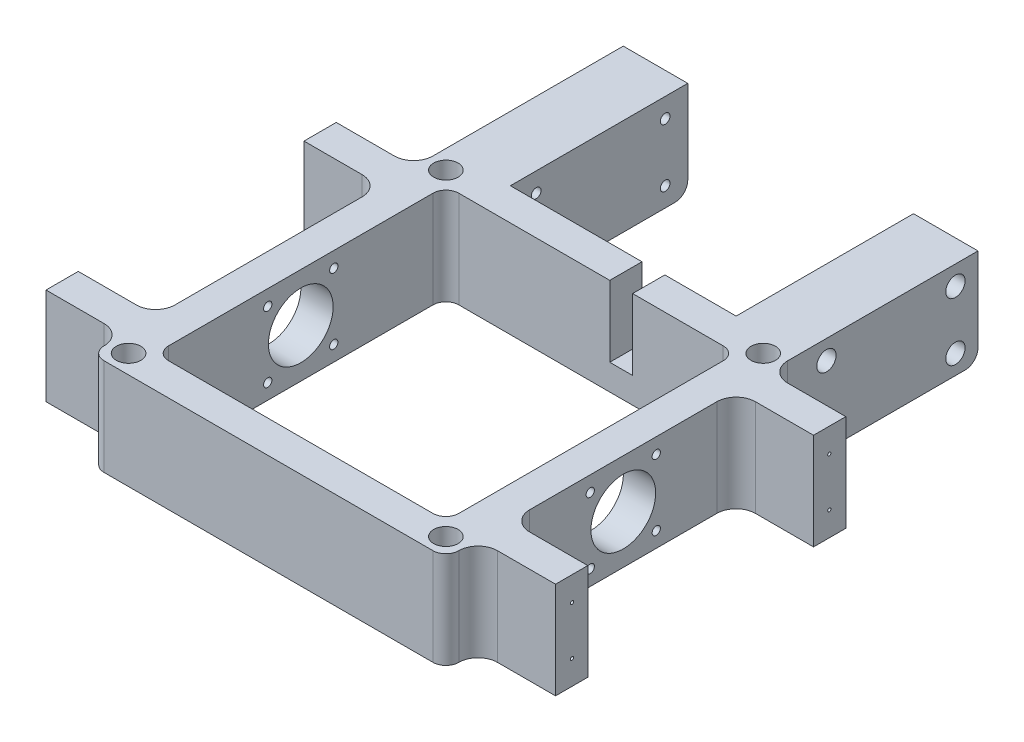
SolidWorks part; units mm, degrees
ref_plane "Front Plane" through (0, 0, 0) normal (0, 0, 1) x (1, 0, 0)
ref_plane "Top Plane" through (0, 0, 0) normal (0, 1, 0) x (1, 0, 0)
ref_plane "Right Plane" through (0, 0, 0) normal (1, 0, 0) x (0, 0, -1)
sketch "Sketch1" plane through (0, 0, 0) normal (0, 1, 0) x (1, 0, 0)
  line L1 (-69.85, 69.85) -> (69.85, 69.85)
  line L2 (-69.85, 69.85) -> (-69.85, -69.85)
  line L3 (-69.85, -69.85) -> (69.85, -69.85)
  line L4 (69.85, 69.85) -> (69.85, -69.85)
  line L5 (-69.85, 69.85) -> (69.85, -69.85) construction
  line L6 (-69.85, -69.85) -> (69.85, 69.85) construction
  line L7 (-69.85, 69.85) -> (-31.75, 69.85)
  line L31 (-69.85, 69.85) -> (-44.45, 69.85)
  line L32 (-69.85, 69.85) -> (-69.85, 139.7)
  line L33 (-69.85, 139.7) -> (-44.45, 139.7)
  line L34 (-44.45, 69.85) -> (-44.45, 139.7)
  line L35 (69.85, 69.85) -> (44.45, 69.85)
  line L36 (69.85, 69.85) -> (69.85, 139.7)
  line L37 (69.85, 139.7) -> (44.45, 139.7)
  line L38 (44.45, 69.85) -> (44.45, 139.7)
  line L39 (-57.15, 57.15) -> (57.15, 57.15)
  line L40 (-57.15, 57.15) -> (-57.15, -57.15)
  line L41 (-57.15, -57.15) -> (57.15, -57.15)
  line L42 (57.15, 57.15) -> (57.15, -57.15)
  line L43 (-57.15, 57.15) -> (57.15, -57.15) construction
  line L44 (-57.15, -57.15) -> (57.15, 57.15) construction
  circle A0 centre (-62.484, -62.484) radius 7.366 construction
  circle A1 centre (-62.484, -62.484) radius 4.826
  circle A2 centre (62.484, -62.484) radius 4.826
  circle A3 centre (62.484, -62.484) radius 7.366 construction
  circle A4 centre (-62.484, 62.484) radius 4.826
  circle A5 centre (-62.484, 62.484) radius 7.366 construction
  circle A6 centre (62.484, 62.484) radius 7.366 construction
  circle A7 centre (62.484, 62.484) radius 4.826
  point P0 (0, 0)
  point P23 (0, 0)
  dimension "D7" = 9.652
  dimension "D8" = 14.732
  dimension "D9" = 9.652
  dimension "D10" = 14.732
  dimension "D11" = 9.652
  dimension "D12" = 14.732
  dimension "D13" = 9.652
  dimension "D15" = 114.3
  dimension "D16" = 114.3
  dimension "D6" = 14.732
  dimension "D1" = 139.7
  dimension "D2" = 139.7
  dimension "D3" = 69.85
  dimension "D4" = 69.85
  dimension "D5" = 88.9
extrude "Boss-Extrude2" add sketch "Sketch1" along normal blind 38.1 contours L1 L34 L33 L32 | L4 L1 L7 L2 L3 A7 A4 A2 A1 L39 L42 L41 L40 | L1 | L35 L38 L37 L36 region at (-57.15, 0, -104.775) region at (-57.15, 0, -67.8743) region at (57.15, 0, -104.775)
sketch "Sketch5" plane through (69.85, 0, 0) normal (1, 0, 0) x (0, 0, -1)
  line L2 (139.7, 38.1) -> (-69.85, 38.1) construction
  line L3 (-13, 6.05) -> (13, 6.05) construction
  line L4 (-13, 6.05) -> (-13, 32.05) construction
  line L5 (-13, 32.05) -> (13, 32.05) construction
  line L6 (13, 6.05) -> (13, 32.05) construction
  line L7 (-13, 6.05) -> (13, 32.05) construction
  line L8 (-13, 32.05) -> (13, 6.05) construction
  circle A0 centre (0, 19.05) radius 12.75
  circle A1 centre (-13, 32.05) radius 1.6319
  circle A2 centre (13, 32.05) radius 1.6319
  circle A3 centre (13, 6.05) radius 1.632
  circle A4 centre (-13, 6.05) radius 1.632
  dimension "D1" = 25.5
  dimension "D2" = 19.05
  dimension ".1160 " = 3.2639
  dimension "D6" = 3.2639
  dimension "D7" = 3.2639
  dimension "D8" = 3.2639
  dimension "D3" = 26
  dimension "D4" = 26
extrude "Cut-Extrude1" cut sketch "Sketch5" against normal up to surface (139.7 mm away) contours A1 | A3 | A4 | A2 | A0 region at (69.85, 32.05, 13) region at (69.85, 32.05, -13) region at (69.85, 6.05, -13) region at (69.85, 6.05, 13) up to face at (-69.85, 19.05, -34.925)
ref_plane "Plane2" through (11.88, 0, 0) normal (-1, 0, 0) x (0, 0, 1)
sketch "Sketch7" plane through (11.88, 0, 0) normal (-1, 0, 0) x (0, 0, 1)
  line L0 (-69.85, 38.1) -> (-69.85, 0) construction
  line L1 (-57.15, 38.1) -> (-57.15, 0) construction
  line L2 (-69.85, 38.1) -> (-69.85, 10.16)
  line L3 (-57.15, 38.1) -> (-57.15, 10.16)
  line L4 (-69.85, 38.1) -> (-57.15, 38.1)
  line L5 (-69.85, 10.16) -> (-57.15, 10.16)
  line L6 (69.85, 0) -> (-139.7, 0) construction
  dimension "D1" = 10.16
extrude "Cut-Extrude2" cut sketch "Sketch7" against normal mid plane 9 contours L4 L3 L5 L2
sketch "Sketch10" plane through (69.85, 0, 0) normal (1, 0, 0) x (0, 0, -1)
  line L0 (139.7, 38.1) -> (139.7, 0) construction
  line L1 (130.81, 7.62) -> (80.01, 7.62) construction
  line L2 (130.81, 7.62) -> (130.81, 30.48) construction
  line L3 (130.81, 30.48) -> (80.01, 30.48) construction
  line L4 (80.01, 7.62) -> (80.01, 30.48) construction
  line L5 (139.7, 0) -> (-69.85, 0) construction
  circle A0 centre (80.01, 30.48) radius 1.905
  circle A1 centre (80.01, 30.48) radius 3.81
  circle A2 centre (130.81, 30.48) radius 1.905
  circle A3 centre (130.81, 7.62) radius 1.905
  circle A4 centre (130.81, 7.62) radius 3.81
  circle A5 centre (130.81, 30.48) radius 3.81
  circle A6 centre (80.01, 7.62) radius 1.905
  circle A7 centre (80.01, 7.62) radius 3.81
  dimension "D5" = 3.81
  dimension "D6" = 3.81
  dimension "D7" = 3.81
  dimension "D8" = 3.81
  dimension "D9" = 7.62
  dimension "D10" = 7.62
  dimension "D11" = 7.62
  dimension "D12" = 7.62
  dimension "D1" = 8.89
  dimension "D2" = 7.62
  dimension "D3" = 22.86
  dimension "D4" = 50.8
extrude "Cut-Extrude3" cut sketch "Sketch10" against normal up to surface (139.7 mm away) contours A0 | A6 | A2 | A3 region at (69.85, 30.48, -80.01) region at (69.85, 7.62, -80.01) up to face at (-69.85, 6.05, -11.3681)
extrude "Cut-Extrude4" cut sketch "Sketch10<3>" against normal blind 15.24
sketch "Sketch10<3>" plane through (69.85, 0, 0) normal (1, 0, 0) x (0, 0, -1) same geometry as "Sketch10"
sketch "Sketch11" plane through (-69.85, 0, 0) normal (-1, 0, 0) x (0, 0, 1)
  line L0 (-80.01, 7.62) -> (-130.81, 7.62) construction
  line L1 (-80.01, 7.62) -> (-80.01, 30.48) construction
  line L2 (-80.01, 30.48) -> (-130.81, 30.48) construction
  line L3 (-130.81, 7.62) -> (-130.81, 30.48) construction
  circle A0 centre (-130.81, 30.48) radius 3.81
  circle A1 centre (-80.01, 7.62) radius 3.81
  circle A2 centre (-80.01, 30.48) radius 3.81
  circle A3 centre (-130.81, 7.62) radius 3.81
  dimension "D1" = 7.62
  dimension "D2" = 7.62
  dimension "D3" = 7.62
  dimension "D4" = 7.62
extrude "Cut-Extrude5" cut sketch "Sketch11" against normal blind 15.24
fillet "Fillet10" radius 5.08 1 edges at (57.15, 19.05, -57.15)
fillet "Fillet11" radius 5.08 1 edges at (-57.15, 19.05, -57.15)
fillet "Fillet12" radius 5.08 1 edges at (-57.15, 19.05, 57.15)
fillet "Fillet13" radius 5.08 1 edges at (57.15, 19.05, 57.15)
fillet "Fillet14" radius 5.08 2 edges at (-57.15, 0, -139.7) (57.15, 0, -139.7)
fillet "Fillet15" radius 5.08 1 edges at (-69.85, 19.05, 69.85) type face fillet first side face at (-69.85, 7.62, -127) second side face at (0, 19.05, 69.85)
fillet "Fillet16" radius 5.08 1 edges at (69.85, 19.05, 69.85) type face fillet first side face at (2.54, 19.05, 69.85) second side face at (69.85, 7.62, -83.82)
sketch "Sketch12" plane through (-69.85, 0, 0) normal (-1, 0, 0) x (0, 0, 1)
  line L0 (0, 19.05) -> (38.1, 19.05) construction
  line L1 (57.15, 0) -> (44.45, 0)
  line L2 (57.15, 0) -> (57.15, 38.1)
  line L3 (57.15, 38.1) -> (44.45, 38.1)
  line L4 (44.45, 0) -> (44.45, 38.1)
  line L5 (57.15, 0) -> (44.45, 38.1) construction
  line L6 (57.15, 38.1) -> (44.45, 0) construction
  line L7 (-44.45, 0) -> (-57.15, 0)
  line L8 (-44.45, 0) -> (-44.45, 38.1)
  line L9 (-44.45, 38.1) -> (-57.15, 38.1)
  line L10 (-57.15, 0) -> (-57.15, 38.1)
  line L11 (-44.45, 0) -> (-57.15, 38.1) construction
  line L12 (-44.45, 38.1) -> (-57.15, 0) construction
  line L13 (0, 19.05) -> (-38.1, 19.05) construction
  line L14 (64.77, 38.1) -> (-139.7, 38.1) construction
  circle A0 centre (0, 19.05) radius 12.75 construction
  point P0 (50.8, 19.05)
  point P5 (-50.8, 19.05)
  dimension "D1" = 38.1
  dimension "D2" = 38.1
  dimension "D3" = 12.7
  dimension "D4" = 12.7
  dimension "D5" = 38.1
  dimension "D6" = 0
  dimension "D7" = 38.1
  dimension "D8" = 0
  dimension "D9" = 0
  dimension "D10" = 50.8
  dimension "D11" = 50.8
extrude "Boss-Extrude3" add sketch "Sketch12" along normal blind 30.48
sketch "Sketch14" plane through (-100.33, 0, 0) normal (-1, 0, 0) x (0, 0, 1)
  line L2 (50.673, 9.525) -> (-50.673, 9.525) construction
  line L3 (50.673, 9.525) -> (50.673, 28.575) construction
  line L4 (50.673, 28.575) -> (-50.673, 28.575) construction
  line L5 (-50.673, 9.525) -> (-50.673, 28.575) construction
  line L6 (50.673, 9.525) -> (-50.673, 28.575) construction
  line L7 (50.673, 28.575) -> (-50.673, 9.525) construction
  circle A2 centre (50.673, 9.525) radius 0.635
  circle A3 centre (50.673, 28.575) radius 0.635
  circle A4 centre (-50.673, 28.575) radius 0.635
  circle A5 centre (-50.673, 9.525) radius 0.635
  point P0 (0, 19.05)
  dimension "D3" = 1.27
  dimension "D1" = 101.346
  dimension "D2" = 19.05
extrude "Cut-Extrude6" cut sketch "Sketch14" against normal blind 25.4 contours A2 | A3 | A4 | A5
mirror "Mirror1" about plane through (0, 0, 0) normal (1, 0, 0) of "Boss-Extrude3", "Cut-Extrude6"
fillet "Fillet17" radius 7.62 1 edges at (-69.85, 19.05, -57.15) type face fillet first side face at (-69.85, 7.62, -127) second side face at (-85.09, 19.05, -57.15)
fillet "Fillet18" radius 7.62 1 edges at (-69.85, 19.05, -44.45) type face fillet first side face at (-85.09, 19.05, -44.45) second side face at (-69.85, 32.05, 14.6319)
fillet "Fillet19" radius 7.62 1 edges at (-69.85, 19.05, 44.45) type face fillet first side face at (-69.85, 32.05, 14.6319) second side face at (-85.09, 19.05, 44.45)
fillet "Fillet20" radius 7.62 1 edges at (-69.85, 19.05, 57.15) type face fillet first side face at (-85.09, 19.05, 57.15) second side face at (-69.85, 19.05, 60.96)
fillet "Fillet21" radius 7.62 1 edges at (69.85, 19.05, 57.15) type face fillet first side face at (69.85, 19.05, 60.96) second side face at (85.09, 19.05, 57.15)
fillet "Fillet22" radius 7.62 1 edges at (69.85, 19.05, 44.45)
fillet "Fillet23" radius 7.62 1 edges at (69.85, 19.05, -57.15)
fillet "Fillet24" radius 7.62 1 edges at (69.85, 19.05, -44.45)
equation "\"D1@Plane2\"=(8.3mm/2)+41.12mm"
